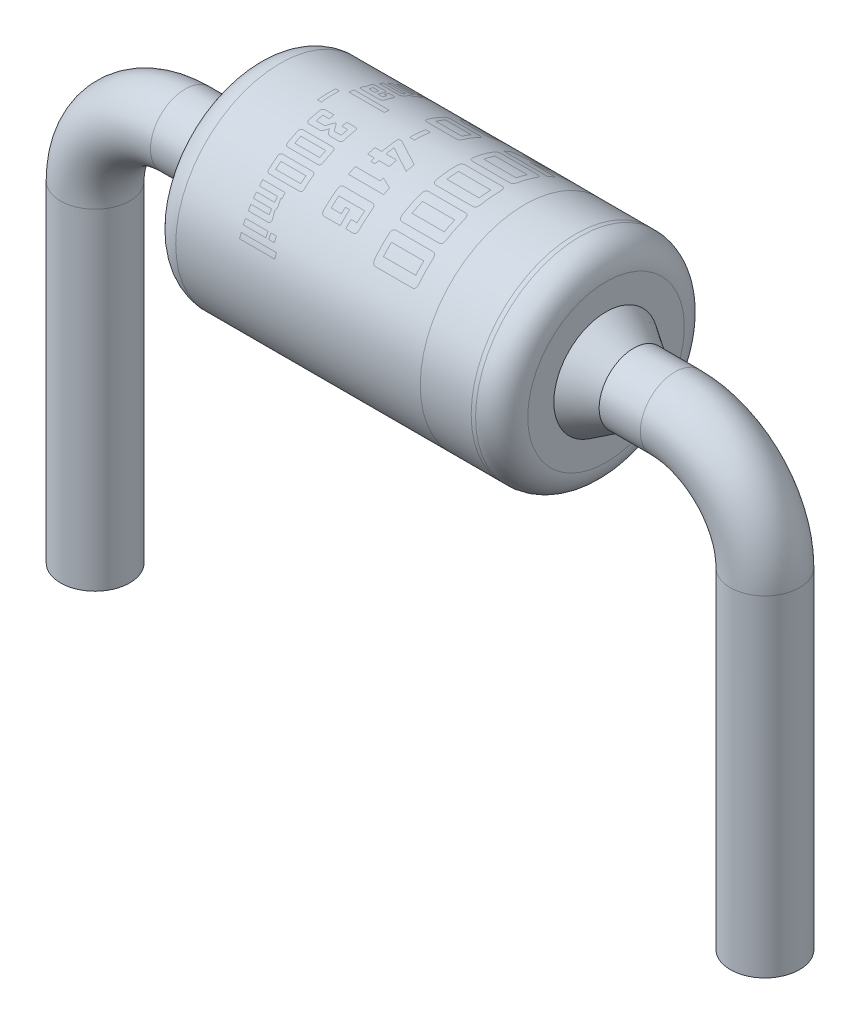
SolidWorks part; units mm, degrees
ref_plane "Front Plane" through (0, 0, 0) normal (0, 0, 1) x (1, 0, 0)
ref_plane "Top Plane" through (0, 0, 0) normal (0, 1, 0) x (1, 0, 0)
ref_plane "Right Plane" through (0, 0, 0) normal (1, 0, 0) x (0, 0, -1)
ref_plane "BODY_RPlane" through (3.81, 0, 0) normal (1, 0, 0) x (0, 0, -1)
sketch "Sketch10" plane through (0, 0, 0) normal (0, 0, 1) x (1, 0, 0)
  line L0 (1.4925, 2.1875) -> (6.1275, 2.1875) construction
  line L1 (3.81, -1.3314) -> (3.81, 1.3314) construction
  line L2 (1.8075, 2.7813) -> (3.81, 2.7812) construction
  line L3 (1.8075, 3.0945) -> (1.8075, 2.5032) construction
  line L4 (2.1044, 3.375) -> (5.5156, 3.375)
  line L6 (1.8075, 3.0781) -> (1.8075, 2.7813)
  line L7 (1.8075, 2.7813) -> (5.8125, 2.7813)
  line L8 (5.8125, 3.0781) -> (5.8125, 2.7813)
  arc A2 (2.1044, 3.375) -> (1.8075, 3.0781) centre (2.1044, 3.0781) ccw
  arc A3 (5.5156, 3.375) -> (5.8125, 3.0781) centre (5.5156, 3.0781) cw
  point P2 (3.81, 2.1875)
  point P14 (3.81, 3.375)
  point P15 (3.81, 2.7812)
  point P18 (3.81, 3.375)
  dimension "D6" = 0.2969
  dimension "D1" = 2.1875
  dimension "D2" = 4.635
  dimension "D4" = 1.1875
  dimension "D5" = 0.315
  dimension "D3" = 0.5938
revolve "BODY_main" add sketch "Sketch10" angle 360 about L0
sketch "Sketch11" plane through (0, 0, 0) normal (0, 0, 1) x (1, 0, 0)
  line L0 (1.4925, 2.1875) -> (1.4925, 2.5813)
  line L1 (1.4925, 2.5813) -> (1.8075, 2.7813)
  line L2 (1.8075, 2.7813) -> (2.0075, 2.7813)
  line L3 (1.4925, 2.1875) -> (2.0075, 2.1875)
  line L5 (2.0075, 2.1875) -> (2.0075, 2.7813)
  line L9 (3.81, -1.3314) -> (3.81, 1.3314) construction
  line L12 (5.6125, 2.1875) -> (5.6125, 2.7813)
  line L13 (6.1275, 2.1875) -> (5.6125, 2.1875)
  line L14 (5.8125, 2.7813) -> (5.6125, 2.7813)
  line L15 (6.1275, 2.5813) -> (5.8125, 2.7813)
  line L16 (6.1275, 2.1875) -> (6.1275, 2.5813)
  dimension "D1" = 0.3937
revolve "BODY_to_PIN" add sketch "Sketch11" angle 360 about L0
ref_plane "TEXT_plane" through (0, 3.475, 0) normal (0, 1, 0) x (1, 0, 0)
sketch "Sketch4"
  dimension "D4" = 7.62
  dimension "D1" = 7.4613
  dimension "D3" = 0.5794
  dimension "D5" = 0.05
  dimension "D6" = 0.1
wrap "TEXT_Wrap" sketch "Sketch4" wrap type scribe source sketch "Sketch4" face at (2.1044, 2.1875, 1.1875)
sketch "Sketch6" plane through (3.81, 0, 0) normal (1, 0, 0) x (0, 0, -1)
  circle A0 centre (0, 2.1875) radius 0.3937
  dimension "D1" = 0.7875
sketch "Sketch7" plane through (0, 0, 0) normal (0, 0, 1) x (1, 0, 0)
  line L0 (6.5963, 2.1875) -> (1.0238, 2.1875)
  line L1 (0, 1.1637) -> (0, -2.6)
  line L2 (3.81, 2.1875) -> (3.81, -2.6) construction
  line L3 (0, -2.6) -> (3.81, -2.6) construction
  line L5 (3.81, -1.3314) -> (3.81, 1.3314) construction
  line L6 (7.62, 1.1638) -> (7.62, -2.6)
  line L9 (1.4925, 2.1875) -> (6.1275, 2.1875) construction
  arc A0 (1.0238, 2.1875) -> (0, 1.1637) centre (1.0238, 1.1637) ccw
  arc A1 (6.5963, 2.1875) -> (7.62, 1.1638) centre (6.5963, 1.1638) cw
  dimension "D3" = 1.0237
  dimension "D1" = 2.6
sweep "PINS" add profiles "Sketch6" path "Sketch7"
equation "\"D4@Sketch7\"=\"PIN_PITCH\""
equation "\"pin_config-----------------\"= 0x000000000000000000000000000000000"
equation "\"PIN_PITCH\"= 300mil"
equation "\"PCB_standoff\"= 1mm"
equation "\"PCB_thickness\"= 1.6mm"
equation "\"PCB_bottom_lead\"= 1.0mm"
equation "\"PIN_C_max\"= 0.863mm"
equation "\"PIN_C_min\"= 0.712mm"
equation "\"body_config----------------\"= 0x000000000000000000000000000000000"
equation "\"BODY_B_max\"= 5.2mm"
equation "\"BODY_B_min\"= 4.07mm"
equation "\"BODY_D_max\"= 2.71mm"
equation "\"BODY_D_min\"= 2.04mm"
equation "\"part_config----------------\"= 0x000000000000000000000000000000000"
equation "\"Component_Size\"= 1"
equation "\"Component_Type\"= 0'variable is not used"
equation "\"auto_calc-------------------\"= 0x000000000000000000000000000000000"
equation "\"BODY_B\"= IIF ( \"Component_Size\" > 0 , IIF ( \"Component_Size\" = 1 , ( ( \"BODY_B_max\" + \"BODY_B_min\" ) / 2 ) , \"BODY_B_max\" ) , \"BODY_B_min\" )'NOT_FOR_USER , AUTOMATIC CALCULATION"
equation "\"BODY_D\"= IIF ( \"Component_Size\" > 0 , IIF ( \"Component_Size\" = 1 , ( ( \"BODY_D_max\" + \"BODY_D_min\" ) / 2 ) , \"BODY_D_max\" ) , \"BODY_D_min\" )'NOT_FOR_USER , AUTOMATIC CALCULATION"
equation "\"PIN_C\"= IIF ( \"Component_Size\" > 0 , IIF ( \"Component_Size\" = 1 , ( ( \"PIN_C_max\" + \"PIN_C_min\" ) / 2 ) , \"PIN_C_max\" ) , \"PIN_C_min\" )'NOT_FOR_USER , AUTOMATIC CALCULATION"
equation "\"PIN_L\"= \"PCB_thickness\" + \"PCB_bottom_lead\"'NOT_FOR_USER , AUTOMATIC CALCULATION"
equation "\"PIN_R\"= \"PIN_C\" * 1.3'NOT_FOR_USER , AUTOMATIC CALCULATION"
equation "\"D1@BODY_RPlane\" = \"PIN_PITCH\" / 2"
equation "\"D1@TEXT_plane\"=\"BODY_D\"+\"PCB_standoff\"+0.1"
equation "\"D1@Sketch4\"=\"BODY_D\" * pi"
equation "\"BODY_CATM_H1\"= \"BODY_B\" / 8'NOT_FOR_USER , AUTOMATIC CALCULATION"
equation "\"D4@Sketch4\"=\"PIN_PITCH\""
equation "\"D1@Sketch6\"=\"PIN_C\""
equation "\"D3@Sketch7\"=\"PIN_R\""
equation "\"D1@Sketch7\"=\"PIN_L\""
equation "\"D2@Sketch10\"=\"BODY_B\""
equation "\"D1@Sketch10\"=(\"BODY_D\" / 2) + \"PCB_standoff\""
equation "\"D4@Sketch10\"=\"BODY_D\"/2"
equation "\"D1@Sketch11\"=\"PIN_C\"/2"
equation "\"D3@Sketch4\"=\"BODY_CATM_H1\""
equation "\"D3@Sketch10\"=\"BODY_D\"/4"
equation "\"D6@Sketch10\"=\"BODY_D\"/8"
equation "\"D5@Sketch10\"=\"PIN_C\"/2.5"
